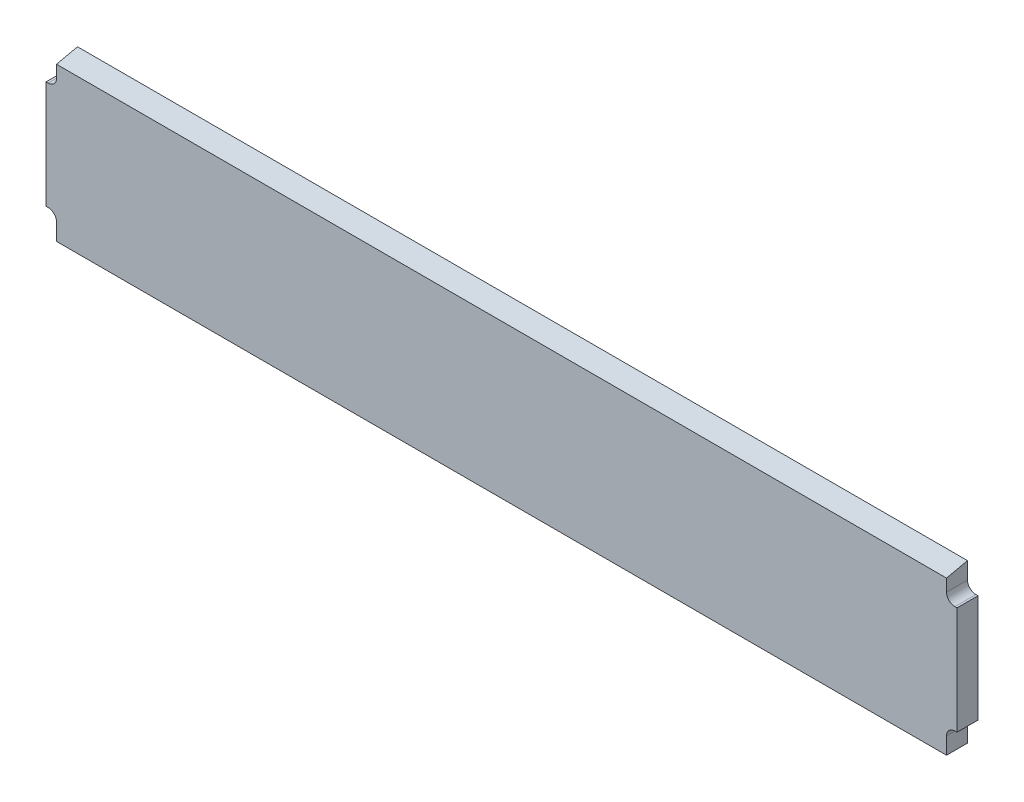
SolidWorks part; units mm, degrees
ref_plane "Front Plane" through (0, 0, 0) normal (0, 0, 1) x (1, 0, 0)
ref_plane "Top Plane" through (0, 0, 0) normal (0, 1, 0) x (1, 0, 0)
ref_plane "Right Plane" through (0, 0, 0) normal (1, 0, 0) x (0, 0, -1)
sketch "Sketch1" plane through (0, 0, 0) normal (0, 0, 1) x (1, 0, 0)
  line L0 (-336.55, -40.7289) -> (-336.55, -59.7789)
  line L1 (336.55, 59.7789) -> (-336.55, 59.7789)
  line L2 (336.55, 59.7789) -> (336.55, 40.7289)
  line L3 (336.55, -59.7789) -> (-336.55, -59.7789)
  line L4 (-336.55, 59.7789) -> (-336.55, 40.7289)
  line L5 (336.55, 59.7789) -> (-336.55, -59.7789) construction
  line L6 (336.55, -59.7789) -> (-336.55, 59.7789) construction
  line L7 (344.4875, 40.7289) -> (336.55, 40.7289)
  line L8 (344.4875, 40.7289) -> (344.4875, -40.7289)
  line L9 (344.4875, -40.7289) -> (336.55, -40.7289)
  line L10 (-344.4875, 40.7289) -> (-344.4875, -40.7289)
  line L11 (344.4875, 40.7289) -> (-344.4875, -40.7289) construction
  line L12 (344.4875, -40.7289) -> (-344.4875, 40.7289) construction
  line L13 (336.55, -40.7289) -> (336.55, -59.7789)
  line L14 (-336.55, 40.7289) -> (-344.4875, 40.7289)
  line L15 (-336.55, -40.7289) -> (-344.4875, -40.7289)
  point P0 (0, 0)
  point P6 (0, 0)
  dimension "D1" = 673.1
  dimension "D2" = 119.5578
  dimension "D3" = 7.9375
  dimension "D4" = 19.05
  dimension "D5" = 688.975
extrude "Boss-Extrude1" add sketch "Sketch1" along normal blind 15.875 contours L1 L4 L14 L10 L15 L0 L3 L13 L9 L8 L7 L2
fillet "Fillet1" radius 6.35 4 edges at (-336.55, -40.7289, 7.9375) (-336.55, 40.7289, 7.9375) (336.55, -40.7289, 7.9375) (336.55, 40.7289, 7.9375)
sketch "Sketch2" plane through (344.4875, 0, 0) normal (1, 0, 0) x (0, 0, -1)
  line L7 (0, 59.7789) -> (-15.875, 56.2595)
  line L8 (-15.875, 59.7789) -> (-15.875, 47.0789) construction
  line L9 (-15.875, 56.2595) -> (-15.875, 59.7789)
  line L10 (-15.875, 59.7789) -> (0, 59.7789)
  dimension "D1" = 12.5
extrude "Cut-Extrude1" cut sketch "Sketch2" against normal through all both and the other way through all
